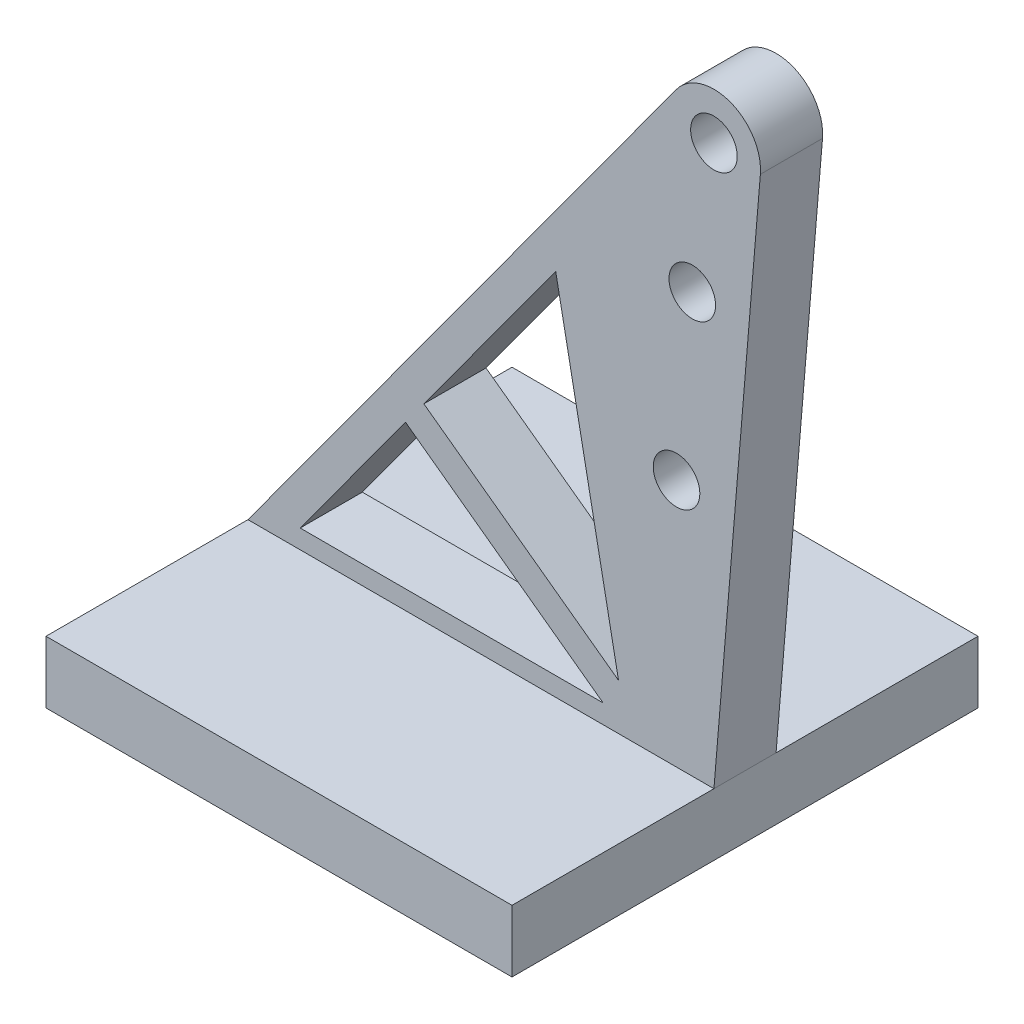
SolidWorks part; units mm, degrees
other "Markup1"
sketch "Sketch4" plane through (-7.5, 21, -7.5) normal (-0.0163, 0.004, -0.9999) x (-0.9959, 0.0889, 0.0166)
other "Markup2"
sketch "Sketch5" plane through (-7.5, 21, -7.5) normal (-0.0163, 0.004, -0.9999) x (-0.9959, 0.0889, 0.0166)
ref_plane "Front Plane" through (0, 0, 0) normal (0, 0, 1) x (1, 0, 0)
ref_plane "Top Plane" through (0, 0, 0) normal (0, 1, 0) x (1, 0, 0)
ref_plane "Right Plane" through (0, 0, 0) normal (1, 0, 0) x (0, 0, -1)
sketch "Sketch1" plane through (0, 0, 0) normal (0, 1, 0) x (1, 0, 0)
  line L1 (-7.5, -7.5) -> (7.5, -7.5)
  line L2 (-7.5, -7.5) -> (-7.5, 7.5)
  line L3 (-7.5, 7.5) -> (7.5, 7.5)
  line L4 (7.5, -7.5) -> (7.5, 7.5)
  line L5 (-7.5, -7.5) -> (7.5, 7.5) construction
  line L6 (-7.5, 7.5) -> (7.5, -7.5) construction
  point P0 (0, 0)
  dimension "D1" = 15
  dimension "D2" = 15
extrude "Boss-Extrude1" add sketch "Sketch1" along normal blind 2
sketch "Sketch2" plane through (0, 0, 0) normal (0, 0, 1) x (1, 0, 0)
  line L0 (0, 0) -> (0, 20) construction
  line L1 (0, 20) -> (7.5, 20) construction
  line L2 (-7.5, 2) -> (6.2886, 20.8845)
  line L3 (-7.5, 2) -> (7.5, 2)
  line L4 (7.5, 2) -> (8.9948, 19.875)
  arc A0 (8.9948, 19.875) -> (6.2886, 20.8845) centre (7.5, 20) ccw
  circle A1 centre (7.5, 20) radius 0.5
  dimension "D3" = 3
  dimension "D4" = 1
  dimension "D1" = 20
  dimension "D2" = 7.5
extrude "Boss-Extrude2" add sketch "Sketch2" along normal mid plane 2 contours L2 A0 L4 L3
sketch "Sketch3" plane through (0, 0, -1) normal (0, 0, -1) x (-1, 0, 0)
  circle A0 centre (-7.5, 20) radius 0.75
  dimension "D1" = 1.5
extrude "Cut-Extrude2" cut sketch "Sketch3" against normal through all
sketch "Sketch6" plane through (0, 0, 1) normal (0, 0, 1) x (1, 0, 0)
  line L0 (-2.4268, 7.2523) -> (-5.8182, 2.6076)
  line L1 (-5.8182, 2.6076) -> (3.9345, 2.6076)
  line L2 (3.9345, 2.6076) -> (-2.4268, 7.2523)
  line L3 (-7.5, 2) -> (6.2886, 20.8845) construction
  line L4 (-1.8371, 8.0599) -> (4.4285, 3.4851)
  line L5 (4.4285, 3.4851) -> (2.4076, 13.8734)
  line L6 (2.4076, 13.8734) -> (-1.8371, 8.0599)
  line L7 (-7.5, 2) -> (7.5, 2) construction
  circle A0 centre (6.8034, 15.5) radius 0.75
  circle A1 centre (6.2959, 10) radius 0.75
  circle A2 centre (7.5, 20) radius 0.75 construction
  point P11 (4.1216, 3.0649)
  point P13 (6.8034, 15.5445)
  point P16 (0, 0)
  dimension "D1" = 1
  dimension "D2" = 1
  dimension "D3" = 1
  dimension "D4" = 13.5
  dimension "D5" = 8
extrude "Cut-Extrude3" cut sketch "Sketch6" against normal blind 70
